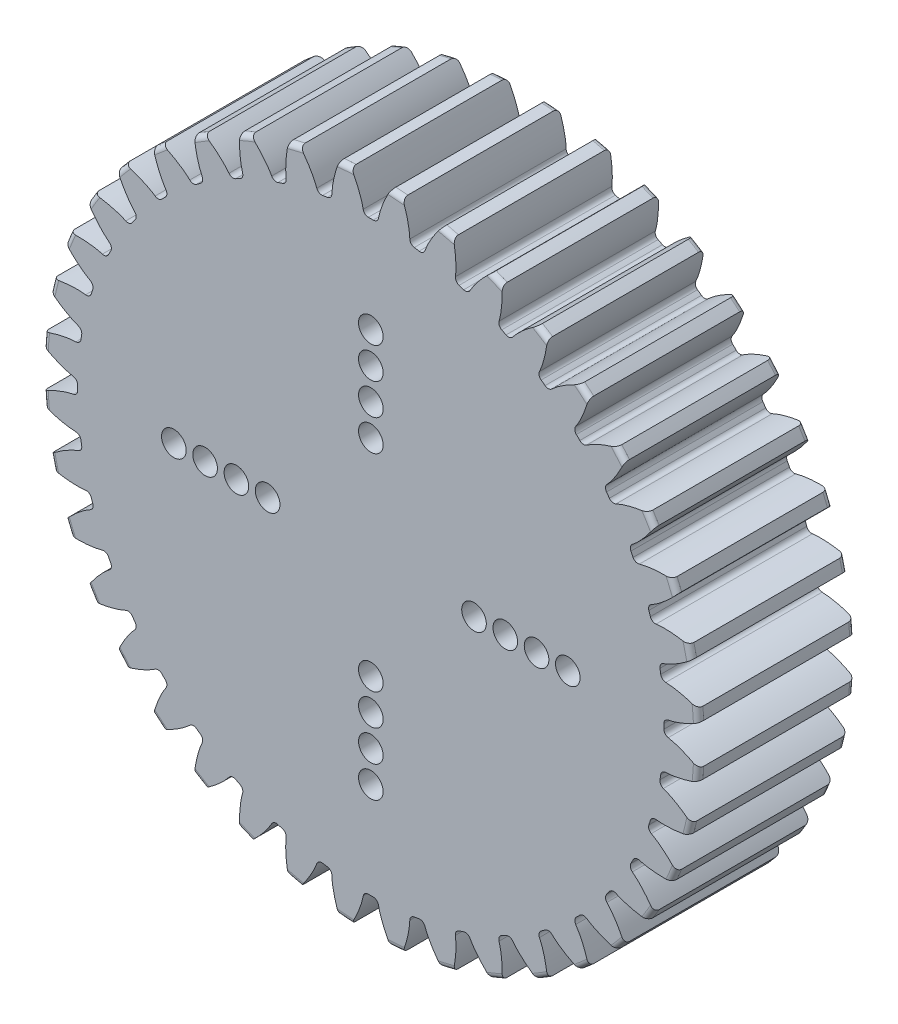
SolidWorks part; units mm, degrees
other "Markup1"
sketch "Sketch10" plane through (-26.67, -26.67, -12.7313) normal (0, 0, -1) x (-1, 0, 0)
ref_plane "Front Plane" through (0, 0, 0) normal (0, 0, 1) x (1, 0, 0)
ref_plane "Top Plane" through (0, 0, 0) normal (0, 1, 0) x (1, 0, 0)
ref_plane "Right Plane" through (0, 0, 0) normal (1, 0, 0) x (0, 0, -1)
sketch "Sketch1" plane through (0, 0, 0) normal (0, 0, 1) x (1, 0, 0)
  line L0 (0, 0) -> (0, 25.4) construction
  line L1 (-8.1634, 28.3712) -> (8.1634, 22.4288) construction
  circle A0 centre (0, 0) radius 23.8125 construction
  circle A1 centre (0, 0) radius 26.67 construction
  circle A2 centre (0, 0) radius 25.4 construction
  circle A3 centre (0, 0) radius 23.8682 construction
  circle A4 centre (0, 0) radius 6.35 construction
  circle A5 centre (0, 0) radius 21.844 construction
  point P8 (254, 0)
  point P13 (508, 0)
  dimension "OD | Outside Diameter" = 53.34
  dimension "Root Diameter" = 47.625
  dimension "Gear Pitch Diameter" = 50.8
  dimension "Base Diameter" = 47.7364
  dimension "For Shaft Diameter" = 12.7
  dimension "Hub Diameter" = 43.688
  dimension "Pressure Angle" = 20
  dimension "Number of Teeth" = 1016
  dimension "Gear Pitch | Diametral Pitch" = 508
sketch "Sketch2" plane through (0, 0, 0) normal (1, 0, 0) x (0, 0, -1)
  line L0 (-12.7, 0) -> (12.7, 0) construction
  line L1 (-12.7, 26.67) -> (12.7, 26.67) construction
  point P2 (0, 26.67)
  point P4 (0, 0)
  point P6 (0, 26.67)
  dimension "Overall Width" = 25.4
  dimension "Hub Width" = 12.7
  dimension "Face Width" = 12.7
sketch "Sketch3" plane through (0, 0, 0) normal (0, 0, 1) x (1, 0, 0)
  circle A0 centre (0, 0) radius 26.67
  circle A1 centre (0, 0) radius 26.67 construction
extrude "Boss-Extrude1" add sketch "Sketch3" against normal up to vertex (12.7 mm away) and the other way up to vertex (12.7 mm away) up to point (0, 0, -12.7) other way up to point (0, 0, 12.7)
sketch "Sketch5" plane through (0, 0, 0) normal (1, 0, 0) x (0, 0, -1)
  line L1 (-12.7, 26.67) -> (0, 26.67)
  line L2 (-12.7, 26.67) -> (-12.7, 21.844)
  line L3 (-12.7, 21.844) -> (0, 21.844)
  line L4 (0, 26.67) -> (0, 21.844)
  line L11 (12.7, 6.35) -> (-12.7, 6.35)
  line L12 (12.7, 6.35) -> (12.7, 0)
  line L13 (12.7, 0) -> (-12.7, 0)
  line L14 (-12.7, 6.35) -> (-12.7, 0)
  point P5 (0, 6.35)
  point P12 (0, 21.844)
revolve "Cut-Revolve1" cut sketch "Sketch5" angle 360 about L0
fillet "Fillet2" radius 0.4261 6 edges at (26.67, 0, -12.7) (6.35, 0, -12.7) (6.35, 0, 12.7) (21.844, 0, 0) (26.67, 0, 0) (21.844, 0, 12.7)
sketch "Sketch4" plane through (0, 0, 0) normal (0, 0, 1) x (1, 0, 0)
  line L0 (0, 0) -> (23.8054, 0.5801) construction
  line L2 (0, 0) -> (23.8054, -0.5801) construction
  line L4 (23.8054, 0.5801) -> (23.8611, 0.5815)
  line L5 (23.8611, -0.5815) -> (23.8054, -0.5801)
  arc A0 (23.8054, 0.5801) -> (23.8054, -0.5801) centre (0, 0) cw
  arc A3 (26.6213, 1.6107) -> (26.6213, -1.6107) centre (0, 0) cw
  circle A4 centre (0, 0) radius 26.67 construction
  spline S0 degree 4 poles (23.8611, 0.5815) (23.8655, 0.5817) (23.8778, 0.5822) (23.901, 0.5839) (23.9389, 0.5874) (23.9871, 0.593) (24.0493, 0.6016) (24.1225, 0.6136) (24.2029, 0.6285) (24.2903, 0.6467) (24.3773, 0.6666) (24.464, 0.6881) (24.5503, 0.711) (24.6546, 0.7404) (24.7796, 0.7781) (24.9253, 0.8257) (25.0903, 0.8838) (25.2579, 0.9474) (25.4225, 1.0136) (25.5884, 1.0847) (25.7486, 1.1565) (25.9145, 1.2353) (26.0673, 1.3103) (26.238, 1.3989) (26.3756, 1.4719) (26.5565, 1.5732) (26.6631, 1.6345) (26.7877, 1.708) (26.8429, 1.7415) (26.8769, 1.7622) knots 0 0 0 0 0 0.005377 0.015084 0.028532 0.04661 0.064855 0.092111 0.119476 0.146842 0.174209 0.201575 0.228941 0.256307 0.307035 0.361767 0.4165 0.471232 0.525964 0.580697 0.635429 0.690161 0.744894 0.799626 0.854358 0.909091 0.954545 1 1 1 1 1 construction
  spline S1 degree 4 poles (23.8611, 0.5815) (23.8655, 0.5817) (23.8778, 0.5822) (23.901, 0.5839) (23.9389, 0.5874) (23.9871, 0.593) (24.0493, 0.6016) (24.1225, 0.6136) (24.2029, 0.6285) (24.2903, 0.6467) (24.3773, 0.6666) (24.464, 0.6881) (24.5503, 0.711) (24.6546, 0.7404) (24.7796, 0.7781) (24.9253, 0.8257) (25.0903, 0.8838) (25.2579, 0.9474) (25.4225, 1.0136) (25.5884, 1.0847) (25.7486, 1.1565) (25.9145, 1.2353) (26.0673, 1.3103) (26.238, 1.3989) (26.3756, 1.4719) (26.5173, 1.5512) (26.5862, 1.5904) (26.6213, 1.6107) knots 0 0 0 0 0 0.005377 0.015084 0.028532 0.04661 0.064855 0.092111 0.119476 0.146842 0.174209 0.201575 0.228941 0.256307 0.307035 0.361767 0.4165 0.471232 0.525964 0.580697 0.635429 0.690161 0.744894 0.799626 0.854358 0.909091 0.909091 0.909091 0.909091 0.909091
  spline S2 degree 4 poles (23.8611, -0.5815) (23.8655, -0.5817) (23.8778, -0.5822) (23.901, -0.5839) (23.9389, -0.5874) (23.9871, -0.593) (24.0493, -0.6016) (24.1225, -0.6136) (24.2029, -0.6285) (24.2903, -0.6467) (24.3773, -0.6666) (24.464, -0.6881) (24.5503, -0.711) (24.6546, -0.7404) (24.7796, -0.7781) (24.9253, -0.8257) (25.0903, -0.8838) (25.2579, -0.9474) (25.4225, -1.0136) (25.5884, -1.0847) (25.7486, -1.1565) (25.9145, -1.2353) (26.0673, -1.3103) (26.238, -1.3989) (26.3756, -1.4719) (26.5565, -1.5732) (26.6631, -1.6345) (26.7877, -1.708) (26.8429, -1.7415) (26.8769, -1.7622) knots 0 0 0 0 0 0.005377 0.015084 0.028532 0.04661 0.064855 0.092111 0.119476 0.146842 0.174209 0.201575 0.228941 0.256307 0.307035 0.361767 0.4165 0.471232 0.525964 0.580697 0.635429 0.690161 0.744894 0.799626 0.854358 0.909091 0.954545 1 1 1 1 1 construction
  spline S3 degree 4 poles (23.8611, -0.5815) (23.8655, -0.5817) (23.8778, -0.5822) (23.901, -0.5839) (23.9389, -0.5874) (23.9871, -0.593) (24.0493, -0.6016) (24.1225, -0.6136) (24.2029, -0.6285) (24.2903, -0.6467) (24.3773, -0.6666) (24.464, -0.6881) (24.5503, -0.711) (24.6546, -0.7404) (24.7796, -0.7781) (24.9253, -0.8257) (25.0903, -0.8838) (25.2579, -0.9474) (25.4225, -1.0136) (25.5884, -1.0847) (25.7486, -1.1565) (25.9145, -1.2353) (26.0673, -1.3103) (26.238, -1.3989) (26.3756, -1.4719) (26.5173, -1.5512) (26.5862, -1.5904) (26.6213, -1.6107) knots 0 0 0 0 0 0.005377 0.015084 0.028532 0.04661 0.064855 0.092111 0.119476 0.146842 0.174209 0.201575 0.228941 0.256307 0.307035 0.361767 0.4165 0.471232 0.525964 0.580697 0.635429 0.690161 0.744894 0.799626 0.854358 0.909091 0.909091 0.909091 0.909091 0.909091
  dimension "D1" = 47.625
extrude "Cut-Extrude1" cut sketch "Sketch4" against normal through all both and the other way through all
fillet "Fillet1" radius 0.4261 2 edges at (23.8054, -0.5801, -6.35) (23.8054, 0.5801, -6.35)
pattern_circular "CirPattern1" count 40 over 360 about axis through (0, 0, 12.7) along (0, 0, -1) of "Cut-Extrude1", "Fillet1"
sketch "Sketch6" plane through (0, 0, 12.7) normal (0, 0, 1) x (1, 0, 0)
  circle A0 centre (0, 0) radius 37.222
extrude "Cut-Extrude2" cut sketch "Sketch6" against normal up to surface (12.7 mm away) up to face at (0, 0, 0)
sketch "Sketch7" plane through (0, 0, 0) normal (0, 0, 1) x (1, 0, 0)
  circle A0 centre (0, 0) radius 13.3299
extrude "Boss-Extrude2" add sketch "Sketch7" against normal up to surface (12.7 mm away) up to face at (0, 0, -12.7)
sketch "Sketch8" plane through (0, 0, 0) normal (0, 0, 1) x (1, 0, 0)
  point P0 (0, 0)
sketch "Sketch9" plane through (0, 0, -12.7) normal (0, 0, -1) x (-1, 0, 0)
  line L0 (-1000, 0) -> (49000, 0) construction
  line L1 (0, -1000) -> (0, 49000) construction
  circle A0 centre (0, 16.002) radius 1
  circle A2 centre (0, 13.462) radius 1
  circle A3 centre (0, 10.922) radius 1
  circle A4 centre (0, 8.382) radius 1
  circle A5 centre (16.002, 0) radius 1
  circle A6 centre (13.462, 0) radius 1
  circle A7 centre (10.922, 0) radius 1
  circle A8 centre (8.382, 0) radius 1
  circle A9 centre (0, -16.002) radius 1
  circle A10 centre (0, -13.462) radius 1
  circle A11 centre (0, -10.922) radius 1
  circle A12 centre (0, -8.382) radius 1
  circle A13 centre (-16.002, 0) radius 1
  circle A14 centre (-13.462, 0) radius 1
  circle A15 centre (-10.922, 0) radius 1
  circle A16 centre (-8.382, 0) radius 1
  point P41 (0, 0)
  dimension "D1" = 16.002
  dimension "D3" = 2.54
  dimension "D6" = 2
  dimension "D2" = 2.54
  dimension "D4" = 2.54
  dimension "D5" = 4
extrude "Cut-Extrude3" cut sketch "Sketch9" against normal up to next
equation "\"Root Diameter@Sketch1\"=\"Root Diameter\""
equation "\"OD | Outside Diameter@Sketch1\"=\"Outside Diameter\""
equation "\"D1@CirPattern1\"=\"Number of Teeth\""
equation "\"Diametral Pitch\"=20"
equation "\"Number of Teeth\"= 40"
equation "\"Pressure Angle\"=20"
equation "\"Pitch Diameter\"= \"Number of Teeth\" / \"Diametral Pitch\""
equation "\"Base Diameter\"= \"Pitch Diameter\" * cos ( \"Pressure Angle\" )"
equation "\"Outside Diameter\"= ( \"Number of Teeth\" + 2 ) / \"Diametral Pitch\""
equation "\"Dedendum\"= 1.25 / \"Diametral Pitch\""
equation "\"Root Diameter\"= \"Pitch Diameter\" - ( 2 * \"Dedendum\" )"
equation "\"Pitch Angle\"= 360deg / \"Number of Teeth\""
equation "\"Alpha\"= sqr ( \"Pitch Diameter\" ^ 2 - \"Base Diameter\" ^ 2 ) / \"Base Diameter\" * 180 / PI - \"Pressure Angle\""
equation "\"Beta\"= ( \"Pitch Angle\" / 4 - \"Alpha\" )"
equation "\"Phi\"= sqr ( ( \"Outside Diameter\" / 2 ) ^ 2 - ( \"Base Diameter\" / 2 ) ^ 2 ) / ( \"Base Diameter\" / 2 )"
equation "\"Addendum\"= 1 / \"Diametral Pitch\""
equation "\"WorkingDepth\"= 2 / \"Diametral Pitch\""
equation "\"WholeDepth\"= 2.25 / \"Diametral Pitch\""
equation "\"Clearance\"= 0.25 / \"Diametral Pitch\""
equation "\"ToothThickness\"= ( pi * 2 ) / \"Diametral Pitch\""
equation "\"CircularPitch\"= pi / \"Diametral Pitch\""
equation "\"Number of Teeth@Sketch1\"=\"Number of Teeth\""
equation "\"Gear Pitch | Diametral Pitch@Sketch1\"=\"Diametral Pitch\""
equation "\"Pressure Angle@Sketch1\"=\"Pressure Angle\""
equation "\"Gear Pitch Diameter@Sketch1\"=\"Pitch Diameter\""
equation "\"Base Diameter@Sketch1\"=\"Base Diameter\""
equation "\"Fillet\"= \"Clearance\" * cos ( \"Pressure Angle\" ) * tan ( ( 90 + \"Pressure Angle\" ) / 2 )"
equation "\"D1@Fillet1\"=\"Fillet\""
equation "\"D1@Sketch4\"=if( \"Base Diameter\">\"Root Diameter\",\"Root Diameter\",\"Base Diameter\"-.00001)"
equation "\"D1@Fillet2\"=\"Fillet\""
